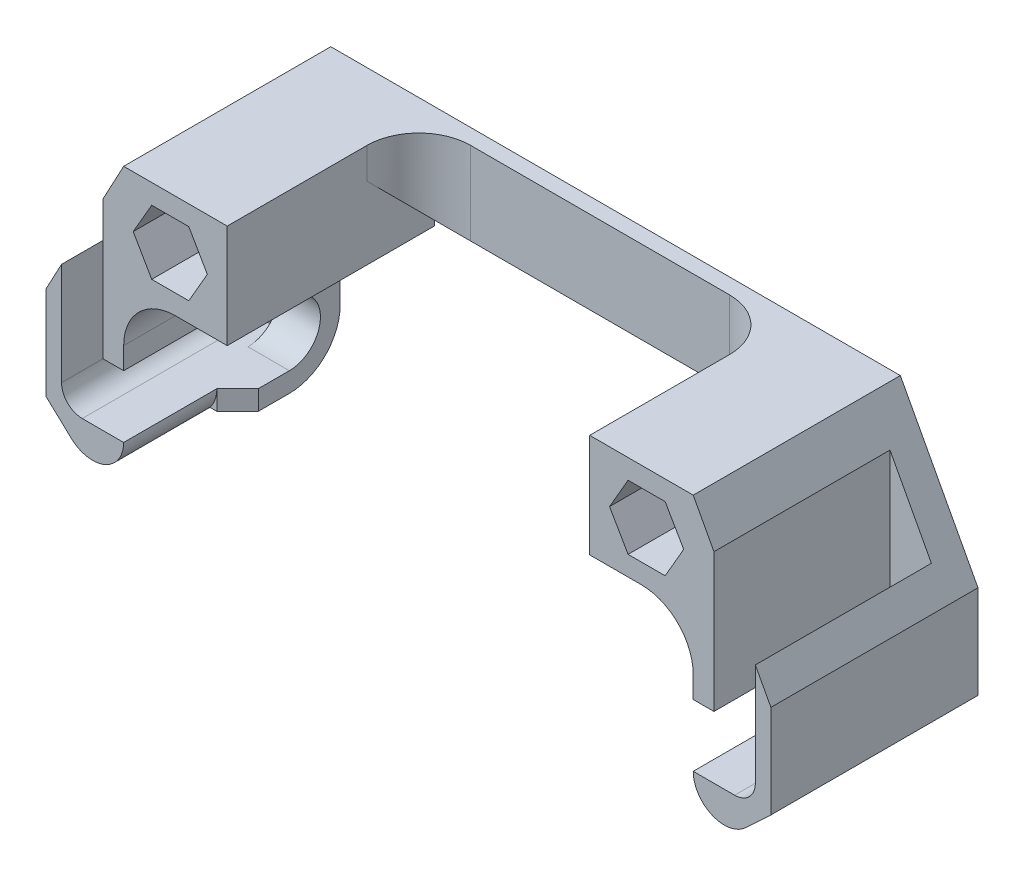
SolidWorks part; units mm, degrees
ref_plane "Front Plane" through (0, 0, 0) normal (0, 0, 1) x (1, 0, 0)
ref_plane "Top Plane" through (0, 0, 0) normal (0, 1, 0) x (1, 0, 0)
ref_plane "Right Plane" through (0, 0, 0) normal (1, 0, 0) x (0, 0, -1)
sketch "Sketch1" plane through (0, 0, 0) normal (0, 0, 1) x (1, 0, 0)
  line L0 (-22.5, 0) -> (22.5, 0)
  line L1 (27.5, -5) -> (27.5, -13.0963)
  line L2 (32.547, -15.2895) -> (35, -13)
  line L3 (35, -13) -> (35, -4)
  line L4 (35, -4) -> (27.5, 10)
  line L5 (27.5, 10) -> (-27.5, 10)
  line L6 (-27.5, 10) -> (-35, -4)
  line L7 (-35, -4) -> (-35, -13)
  line L8 (-35, -13) -> (-32.547, -15.2895)
  line L9 (-27.5, -13.0963) -> (-27.5, -5)
  line L10 (-27.5, 10) -> (-27.5, 0) construction
  line L11 (27.5, 10) -> (27.5, 0) construction
  line L12 (-35, -4) -> (35, -4) construction
  line L13 (0, -4) -> (0, 0) construction
  line L14 (-27.5, -20) -> (27.5, -20) construction
  line L15 (-35, -13) -> (35, -13) construction
  arc A0 (27.5, -13.0963) -> (32.547, -15.2895) centre (30.5, -13.0963) ccw
  arc A1 (-32.547, -15.2895) -> (-27.5, -13.0963) centre (-30.5, -13.0963) ccw
  arc A2 (22.5, 0) -> (27.5, -5) centre (22.5, -5) cw
  arc A3 (-22.5, 0) -> (-27.5, -5) centre (-22.5, -5) ccw
  dimension "D6" = 3
  dimension "D7" = 5
  dimension "D1" = 70
  dimension "D2" = 55
  dimension "D3" = 20
  dimension "D4" = 9
  dimension "D5" = 10
  dimension "D8" = 4
extrude "Boss-Extrude1" add sketch "Sketch1" along normal blind 20
sketch "Sketch3" plane through (0, 0, 0) normal (0, -1, 0) x (1, 0, 0)
  line L0 (-22.5, 20) -> (22.5, 20) construction
  line L1 (-17.5, 20) -> (17.5, 20)
  line L2 (-17.5, 20) -> (-17.5, 1.5)
  line L3 (-17.5, 1.5) -> (17.5, 1.5)
  line L4 (17.5, 20) -> (17.5, 1.5)
  line L5 (0, 1.5) -> (0, 0) construction
  line L6 (-22.5, 0) -> (22.5, 0) construction
  dimension "D1" = 35
  dimension "D2" = 1.5
extrude "Cut-Extrude2" cut sketch "Sketch3" against normal through all
sketch "Sketch2" plane through (0, 0, 20) normal (0, 0, 1) x (1, 0, 0)
  line L1 (-27.5, -13.0963) -> (-30.5295, -13.0963)
  line L2 (-27.5, -13.0963) -> (-27.5, -7.0963)
  line L3 (-27.5, -7.0963) -> (-29.5, -7.0963)
  line L5 (-30.5295, -13.0963) -> (-31.5, -13.0963)
  line L6 (-29.5, -7.0963) -> (-29.5, 8.5948)
  line L7 (-29.5, 8.5948) -> (-33.5, 8.5948)
  line L8 (-33.5, -11.0963) -> (-33.5, 8.5948)
  arc A0 (-31.5, -13.0963) -> (-33.5, -11.0963) centre (-31.5, -11.0963) cw
  dimension "D4" = 2
  dimension "D1" = 6
  dimension "D2" = 4
  dimension "D3" = 2
extrude "Cut-Extrude1" cut sketch "Sketch2" against normal blind 17
mirror "Mirror1" about plane through (0, 0, 0) normal (1, 0, 0) of "Cut-Extrude1"
sketch "Sketch5" plane through (0, 0, 20) normal (0, 0, 1) x (1, 0, 0)
  line L0 (-23, 5) -> (23, 5) construction
  line L1 (0, 5) -> (0, 0) construction
  circle A0 centre (-23, 5) radius 1.75
  circle A1 centre (23, 5) radius 1.75
  dimension "D3" = 3.5
  dimension "D1" = 5
  dimension "D2" = 46
extrude "Cut-Extrude4" cut sketch "Sketch5" against normal through all
sketch "Sketch6" plane through (0, 0, 20) normal (0, 0, 1) x (1, 0, 0)
  line L1 (-19.4204, 5) -> (-21.2102, 8.1)
  line L2 (-21.2102, 8.1) -> (-24.7898, 8.1)
  line L3 (-24.7898, 8.1) -> (-26.5796, 5)
  line L4 (-26.5796, 5) -> (-24.7898, 1.9)
  line L5 (-24.7898, 1.9) -> (-21.2102, 1.9)
  line L6 (-21.2102, 1.9) -> (-19.4204, 5)
  line L7 (19.4204, 5) -> (21.2102, 1.9)
  line L8 (21.2102, 1.9) -> (24.7898, 1.9)
  line L9 (24.7898, 1.9) -> (26.5796, 5)
  line L10 (26.5796, 5) -> (24.7898, 8.1)
  line L11 (24.7898, 8.1) -> (21.2102, 8.1)
  line L12 (21.2102, 8.1) -> (19.4204, 5)
  circle A0 centre (-23, 5) radius 3.1 construction
  circle A1 centre (23, 5) radius 3.1 construction
  dimension "D1" = 6.2
extrude "Cut-Extrude5" cut sketch "Sketch6" against normal blind 15
chamfer "Chamfer1" distance 2 angle 45 1 edges at (0, 0, 1.5)
fillet "Fillet1" radius 5 2 edges at (17.5, 6, 1.5) (-17.5, 6, 1.5)
sketch "Sketch7" plane through (-27.5, 0, 0) normal (1, 0, 0) x (0, 0, -1)
  line L0 (-3, -13.0963) -> (-3, -7.0963) construction
  line L1 (-1.1, -10.0963) -> (-1.1, 0)
  line L2 (-20, 0) -> (0, 0) construction
  line L3 (-1.1, 0) -> (-11, 0)
  line L4 (-20, 0) -> (0, 0) construction
  line L5 (-6, -5.1963) -> (-6, -14.9963) construction
  line L7 (-11, -5.1963) -> (-11, -7.0963)
  line L8 (-3, -7.0963) -> (-20, -7.0963) construction
  line L9 (-11, -7.0963) -> (-6, -7.0963)
  line L10 (-6, -14.9963) -> (-11, -14.9963)
  line L11 (-11, -14.9963) -> (-11, -13.0963)
  line L12 (-20, -13.0963) -> (-3, -13.0963) construction
  line L13 (-11, -13.0963) -> (-6, -13.0963)
  line L14 (-11, -13.0963) -> (-11, -7.0963) construction
  line L15 (-11, 0) -> (-11, -5.1963)
  arc A0 (-6, -13.0963) -> (-6, -7.0963) centre (-6, -10.0963) ccw
  arc A1 (-6, -14.9963) -> (-1.1, -10.0963) centre (-6, -10.0963) ccw
  circle A2 centre (-6, -10.0963) radius 3 construction
  circle A3 centre (-6, -10.0963) radius 4.9 construction
  dimension "D2" = 5
  dimension "D1" = 1.9
extrude "Boss-Extrude5" add sketch "Sketch7" along normal blind 2 and the other way up to vertex (2 mm away) contours L13 A0 L9 L7 L15 L3 L1 A1 L10 L11 other way up to point (-29.5, -7.0963, 20)
mirror "Mirror4" about plane through (0, 0, 0) normal (1, 0, 0) of "Boss-Extrude5"
chamfer "Chamfer2" distance 2 angle 45 4 edges at (25.5, -14.0463, 11) (25.5, -4.0482, 11) (-25.5, -4.0482, 11) (-25.5, -14.0463, 11)
